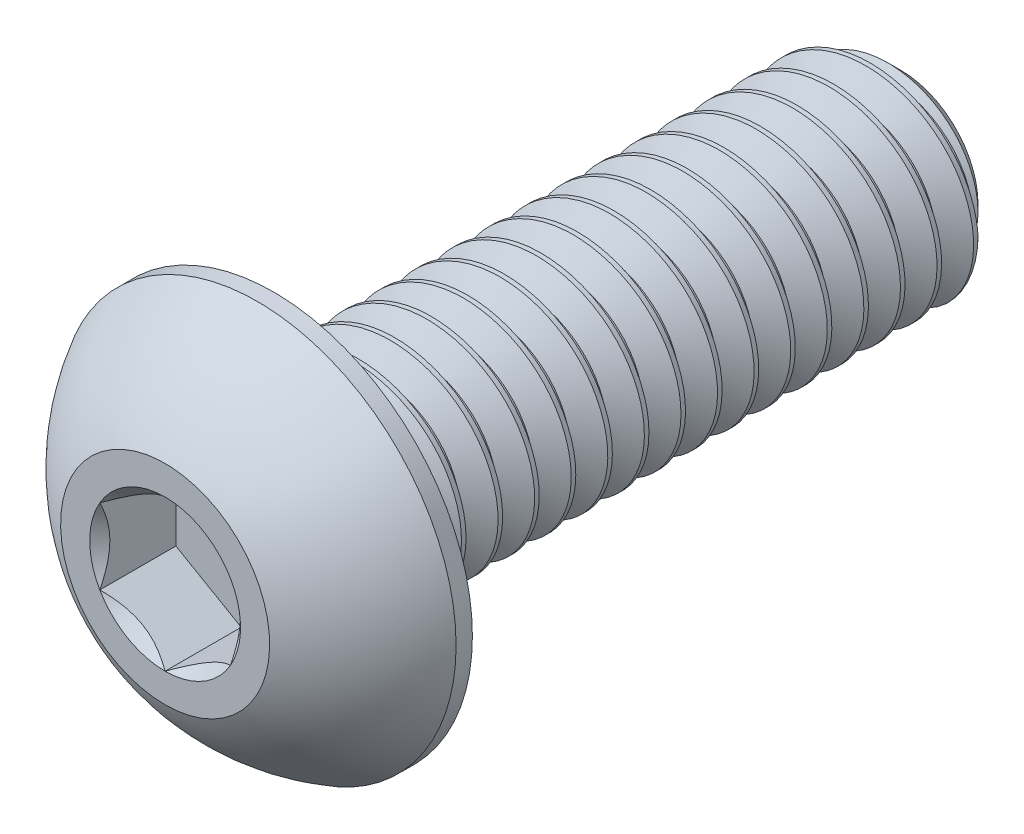
SolidWorks part; units mm, degrees
ref_plane "Front" through (0, 0, 0) normal (0, 0, 1) x (1, 0, 0)
ref_plane "Top" through (0, 0, 0) normal (0, 1, 0) x (1, 0, 0)
ref_plane "Right" through (0, 0, 0) normal (1, 0, 0) x (0, 0, -1)
sketch "Sketch1" plane through (0, 0, 0) normal (1, 0, 0) x (0, 0, -1)
  line L2 (2.08, 2) -> (14.08, 2)
  line L3 (14.08, 2) -> (14.08, 0)
  line L4 (14.08, 0) -> (2.08, 0)
  line L6 (1.768, 3.8) -> (2.08, 3.8) construction
  line L7 (14.08, 2) -> (14.08, -2) construction
  line L8 (0, 0) -> (2.08, 0) construction
  line L9 (2.08, 3.8) -> (2.08, -3.8) construction
  line L11 (2.08, 2) -> (2.08, 0)
  line L13 (0, 1.25) -> (0, -1.25) construction
  line L14 (0, 1.25) -> (0, 2) construction
  arc A3 (0, 2) -> (1.768, 3.8) centre (3.8365, 0) cw construction
  dimension "D1" = 0.312
  dimension "Head Ht" = 2.08
  dimension "Head Dia" = 7.6
  dimension "Dia" = 4
  dimension "Lg" = 12
  dimension "Hex" = 2.5
revolve "Revolve1" add sketch "Sketch1" angle 360 mid plane about L4
sketch "Sketch3" plane through (0, 0, -14.08) normal (0, 0, -1) x (-1, 0, 0)
  circle A0 centre (0, 0) radius 2
curve "Helix/Spiral1" pitch 0.7 height 12.7 radius 2 centre (0, 0, -14.08) axis (0, 0, 1) start towards (0, 1, 0)
sketch "Sketch2" plane through (0, 0, 0) normal (1, 0, 0) x (0, 0, -1)
  line L0 (14.08, 2) -> (14.6925, 2)
  line L1 (14.6925, 2) -> (14.43, 1.5453)
  line L2 (14.43, 1.5453) -> (14.3425, 1.5453)
  line L3 (14.3425, 1.5453) -> (14.08, 2)
  line L4 (14.2112, 1.7727) -> (14.5612, 1.7727) construction
  dimension "D1" = 60
  dimension "D2" = 0.0875
  dimension "D3" = 0.35
chamfer "Chamfer1" distance 0.525 angle 45 1 edges at (0, 2, -14.08)
sweep "Cut-Sweep1" cut profiles "Sketch2" path "Helix/Spiral1" align with end faces yes
sketch "Sketch7" plane through (0, 0, 0) normal (1, 0, 0) x (0, 0, -1)
  line L6 (1.768, 3.8) -> (2.08, 3.8) construction
  line L8 (0, 0) -> (2.08, 0) construction
  line L11 (2.08, 3.8) -> (2.08, -3.8) construction
  line L12 (1.768, 3.8) -> (2.08, 3.8)
  line L13 (0, 0) -> (2.08, 0)
  line L14 (0, 1.25) -> (0, -1.25) construction
  line L15 (2.08, 3.8) -> (2.08, 0)
  line L16 (0, 2) -> (0, 0)
  arc A2 (1.768, 3.8) -> (0, 2) centre (3.8365, 0) ccw construction
  arc A3 (1.768, 3.8) -> (0, 2) centre (3.8365, 0) ccw
revolve "Revolve2" add sketch "Sketch7" angle 360 mid plane about L13
sketch "Sketch5" plane through (0, 0, 0) normal (0, 0, 1) x (1, 0, 0)
  line L1 (1.25, -0.7217) -> (1.25, 0.7217)
  line L2 (1.25, 0.7217) -> (0, 1.4434)
  line L3 (0, 1.4434) -> (-1.25, 0.7217)
  line L4 (-1.25, 0.7217) -> (-1.25, -0.7217)
  line L5 (-1.25, -0.7217) -> (0, -1.4434)
  line L6 (0, -1.4434) -> (1.25, -0.7217)
  circle A0 centre (0, 0) radius 1.25 construction
extrude "Cut-Extrude2" cut sketch "Sketch5" against normal blind 1.456
sketch "Sketch6" plane through (0, 0, 0) normal (0, 0, 1) x (1, 0, 0)
  circle A0 centre (0, 0) radius 1.4434
extrude "Cut-Extrude3" cut sketch "Sketch6" against normal blind 1.456 draft 45
sketch "Sketch9" [suppressed] plane through (0, 0, -6.6) normal (0, 0, 1) x (1, 0, 0)
  circle A2 centre (0, 0) radius 6
extrude "Boss-Extrude2" [suppressed] add sketch "Sketch9" against normal offset from surface (19 mm away) 32 up to face at (0, 1.475, -14.08)
sketch "Sketch10" plane through (0, 0, 0) normal (1, 0, 0) x (0, 0, -1)
  line L0 (14.08, 2) -> (14.08, -2) construction
  point P0 (13.03, -2)
  dimension "D1" = 1.05
equation "\"D3@Helix/Spiral1\" = \"Lg@Sketch1\" + \"D4@Helix/Spiral1\""
equation "\"D2@Sketch2\" = \"D4@Helix/Spiral1\" * .125"
equation "\"D3@Sketch2\" = \"D4@Helix/Spiral1\" * .5"
equation "\"D1@Chamfer1\" = \"D4@Helix/Spiral1\" * .75"
equation "\"D1@Cut-Extrude2\" = \"Head Ht@Sketch1\" * .7"
equation "\"D1@Sketch1\" = \"Head Ht@Sketch1\" * .15"
equation "\"D1@Sketch10\" = \"D4@Helix/Spiral1\" * 1.5"
equation "\"D1@Cut-Extrude3\" = \"D1@Cut-Extrude2\""
